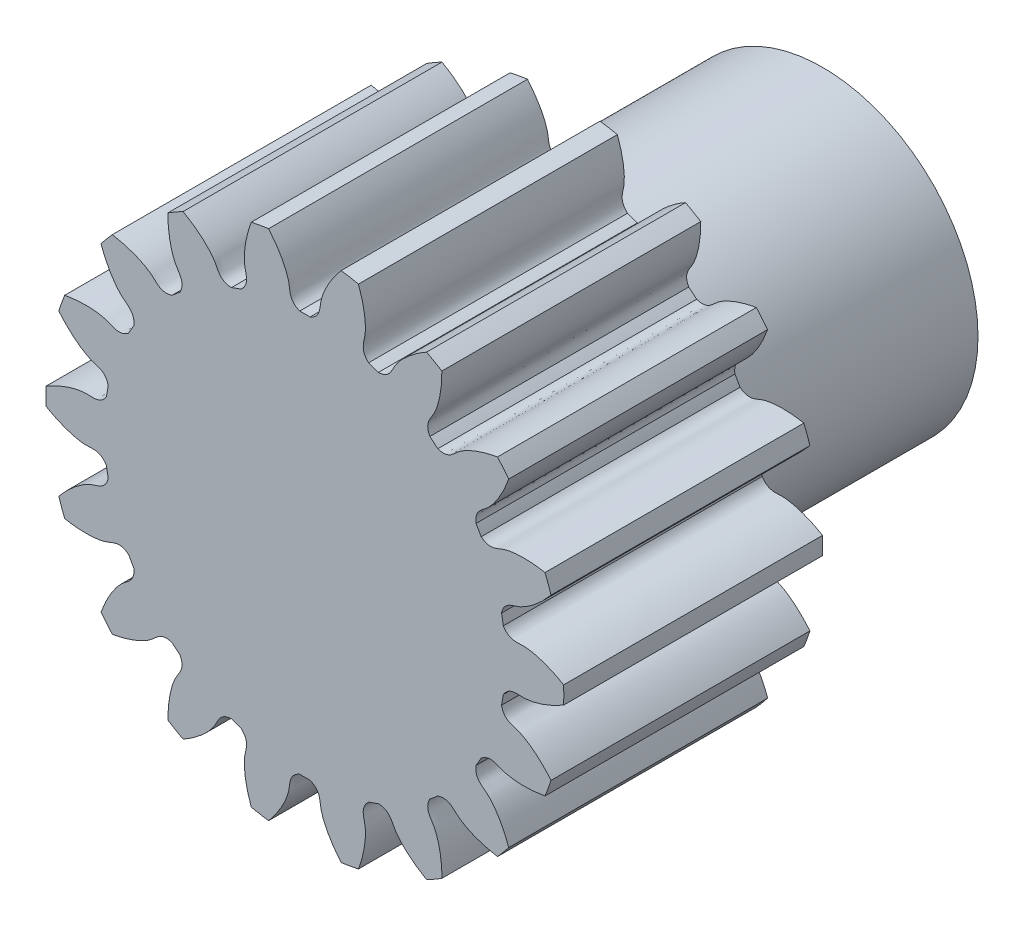
SolidWorks part; units mm, degrees
ref_plane "前视基准面" through (0, 0, 0) normal (0, 0, 1) x (1, 0, 0)
ref_plane "上视基准面" through (0, 0, 0) normal (0, 1, 0) x (1, 0, 0)
ref_plane "右视基准面" through (0, 0, 0) normal (1, 0, 0) x (0, 0, -1)
sketch "草图1" plane through (0, 0, 0) normal (0, 0, 1) x (1, 0, 0)
  circle A0 centre (0, 0) radius 5
extrude "凸台-拉伸1" add sketch "草图1" along normal blind 5
ref_axis "基准轴1" through (0, 0, 5) along (0, 0, -1)
sketch "草图2" plane through (0, 0, 0) normal (0, 0, 1) x (1, 0, 0)
  line L0 (0, 0) -> (0, 5) construction
  circle A0 centre (0, 0) radius 5 construction
  arc A1 (0.0997, 3.8737) -> (-0.0997, 3.8737) centre (0, 0) ccw
  arc A2 (1.5493, 5.6533) -> (-1.5493, 5.6533) centre (0, 0) ccw
  spline S0 degree 3 poles (0.0997, 3.8737) (0.3076, 3.9593) (0.2814, 4.1193) (0.3159, 4.2713) (0.3194, 4.2853) (0.3236, 4.3008) (0.3285, 4.3178) (0.3343, 4.3364) (0.341, 4.3564) (0.3487, 4.378) (0.3574, 4.4009) (0.3672, 4.4252) (0.3781, 4.4509) (0.3903, 4.4779) (0.4037, 4.5062) (0.4184, 4.5357) (0.4345, 4.5664) (0.452, 4.5982) (0.471, 4.6312) (0.4916, 4.6653) (0.5137, 4.7003) (0.5374, 4.7363) (0.5628, 4.7733) (0.5899, 4.8111) (0.6188, 4.8496) (0.6495, 4.889) (0.6821, 4.929) (0.7165, 4.9697) (0.7529, 5.0109) (0.7912, 5.0527) (0.8315, 5.0949) (0.8738, 5.1374) (0.9182, 5.1803) (0.9647, 5.2235) (1.0133, 5.2668) (1.0641, 5.3103) (1.117, 5.3538) (1.1721, 5.3973) (1.2294, 5.4407) (1.289, 5.4839) (1.3507, 5.527) (1.437, 5.5845) (1.5038, 5.6262) (1.5493, 5.6533) knots 0 0 0 0 0.187592 0.192996 0.199121 0.205966 0.213531 0.221818 0.230824 0.240552 0.250999 0.262168 0.274057 0.286666 0.299996 0.314047 0.328818 0.344309 0.360521 0.377454 0.395107 0.413481 0.432575 0.45239 0.472926 0.494181 0.516158 0.538855 0.562272 0.58641 0.611269 0.636848 0.663148 0.690168 0.717909 0.74637 0.775552 0.805454 0.836077 0.867421 0.899485 0.932269 1 1 1 1
  spline S1 degree 3 poles (-0.0997, 3.8737) (-0.3076, 3.9593) (-0.2814, 4.1193) (-0.3159, 4.2713) (-0.3194, 4.2853) (-0.3236, 4.3008) (-0.3285, 4.3178) (-0.3343, 4.3364) (-0.341, 4.3564) (-0.3487, 4.378) (-0.3574, 4.4009) (-0.3672, 4.4252) (-0.3781, 4.4509) (-0.3903, 4.4779) (-0.4037, 4.5062) (-0.4184, 4.5357) (-0.4345, 4.5664) (-0.452, 4.5982) (-0.471, 4.6312) (-0.4916, 4.6653) (-0.5137, 4.7003) (-0.5374, 4.7363) (-0.5628, 4.7733) (-0.5899, 4.8111) (-0.6188, 4.8496) (-0.6495, 4.889) (-0.6821, 4.929) (-0.7165, 4.9697) (-0.7529, 5.0109) (-0.7912, 5.0527) (-0.8315, 5.0949) (-0.8738, 5.1374) (-0.9182, 5.1803) (-0.9647, 5.2235) (-1.0133, 5.2668) (-1.0641, 5.3103) (-1.117, 5.3538) (-1.1721, 5.3973) (-1.2294, 5.4407) (-1.289, 5.4839) (-1.3507, 5.527) (-1.437, 5.5845) (-1.5038, 5.6262) (-1.5493, 5.6533) knots 0 0 0 0 0.187592 0.192996 0.199121 0.205966 0.213531 0.221818 0.230824 0.240552 0.250999 0.262168 0.274057 0.286666 0.299996 0.314047 0.328818 0.344309 0.360521 0.377454 0.395107 0.413481 0.432575 0.45239 0.472926 0.494181 0.516158 0.538855 0.562272 0.58641 0.611269 0.636848 0.663148 0.690168 0.717909 0.74637 0.775552 0.805454 0.836077 0.867421 0.899485 0.932269 1 1 1 1
extrude "切除-拉伸1" cut sketch "草图2" along normal through all
pattern_circular "阵列(圆周)1" count 18 every 20 about axis through (0, 0, 5) along (0, 0, -1) of "切除-拉伸1"
sketch "草图3" plane through (0, 0, 0) normal (0, 0, 1) x (1, 0, 0)
  circle A0 centre (0, 0) radius 4.5 construction
  dimension "Dn" = 9
sketch "草图4" plane through (0, 0, 0) normal (0, 0, -1) x (-1, 0, 0)
  circle A0 centre (0, 0) radius 3
  dimension "D1" = 6
extrude "凸台-拉伸2" add sketch "草图4" along normal blind 5
sketch "草图5" plane through (0, 0, -5) normal (0, 0, -1) x (-1, 0, 0)
  circle A0 centre (0, 0) radius 1
  dimension "D1" = 2
extrude "切除-拉伸2" cut sketch "草图5" against normal blind 5
